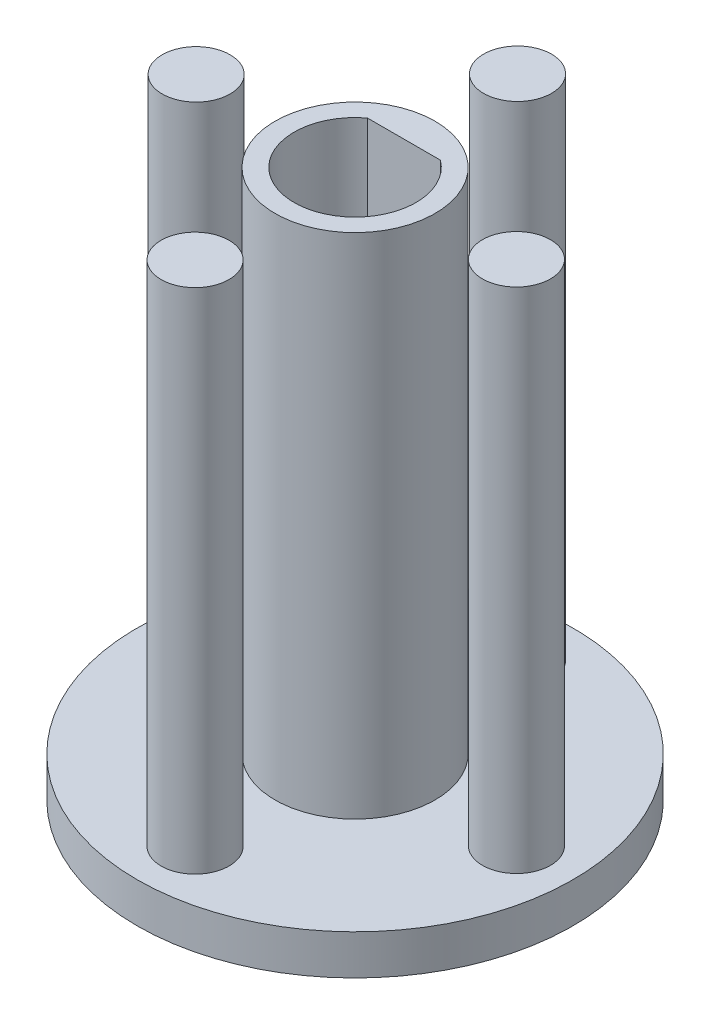
SolidWorks part; units mm, degrees
ref_plane "Front Plane" through (0, 0, 0) normal (0, 0, 1) x (1, 0, 0)
ref_plane "Top Plane" through (0, 0, 0) normal (0, 1, 0) x (1, 0, 0)
ref_plane "Right Plane" through (0, 0, 0) normal (1, 0, 0) x (0, 0, -1)
sketch "Sketch3" plane through (0, 0, 0) normal (0, 1, 0) x (1, 0, 0)
  line L0 (-7.9995, 0.0532) -> (0.009, 8.1156) construction
  line L1 (0.009, 8.1156) -> (8.0177, 0.0533) construction
  line L2 (8.0177, 0.0533) -> (0.0092, -8.0091) construction
  line L3 (0.0092, -8.0091) -> (-7.9995, 0.0532) construction
  line L7 (18.7783, 0.0532) -> (-25.5315, 0.0532) construction
  line L8 (9.7482, 0.0532) -> (10.8982, 0.0532)
  line L9 (-1.8231, 2.4452) -> (1.8231, 2.4452)
  line L11 (0.009, -13.1564) -> (0.009, 16.0208) construction
  circle A0 centre (0, 0) radius 10.9
  circle A1 centre (0.009, 8.1156) radius 1.7
  circle A2 centre (8.0177, 0.0533) radius 1.7
  circle A3 centre (0.0092, -8.0091) radius 1.7
  circle A4 centre (-7.9995, 0.0532) radius 1.7
  circle A5 centre (0, 0) radius 4
  arc A6 (-1.8231, 2.4452) -> (1.8231, 2.4452) centre (0, 0) ccw
  dimension "D1" = 21.8
extrude "Boss-Extrude1" add sketch "Sketch3" along normal blind 27.4 contours A4 | A3 | A2 | A1 | A6 L9 | A5
extrude "Boss-Extrude2" add sketch "Sketch3<17>" along normal blind 2 contours A0
sketch "Sketch3<17>" plane through (0, 0, 0) normal (0, 1, 0) x (1, 0, 0) same geometry as "Sketch3"
